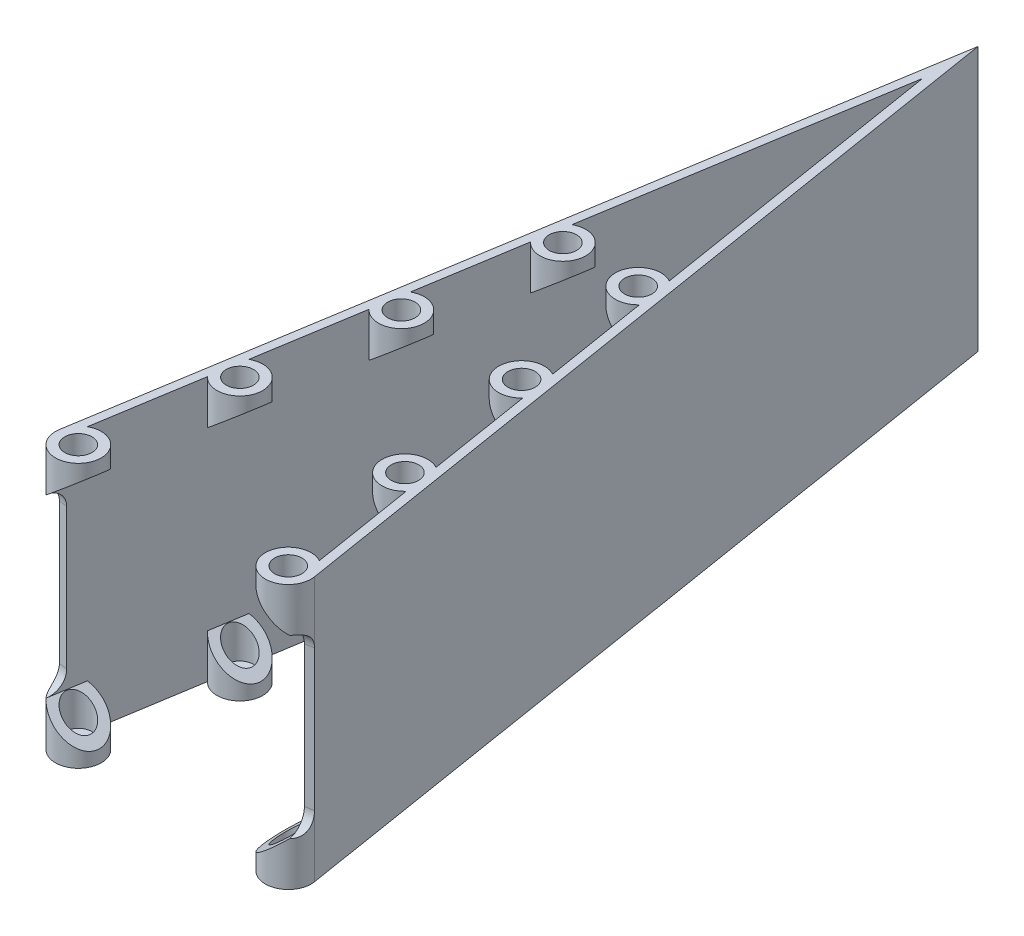
SolidWorks part; units mm, degrees
ref_plane "Front Plane" through (0, 0, 0) normal (0, 0, 1) x (1, 0, 0)
ref_plane "Top Plane" through (0, 0, 0) normal (0, 1, 0) x (1, 0, 0)
ref_plane "Right Plane" through (0, 0, 0) normal (1, 0, 0) x (0, 0, -1)
sketch "Sketch1" plane through (0, 0, 0) normal (0, 1, 0) x (1, 0, 0)
  line L0 (-13.5, 0) -> (13.5, 0) construction
  line L1 (-13.5, 0) -> (0, 83.7185)
  line L2 (0, 83.7185) -> (13.5, 0)
  line L3 (13.5, 0) -> (14.4872, 0.1592)
  line L4 (14.4872, 0.1592) -> (0, 90)
  line L5 (0, 90) -> (-14.4872, 0.1592)
  line L6 (-14.4872, 0.1592) -> (-13.5, 0)
  point P2 (0, 0)
  dimension "D1" = 90
  dimension "D2" = 90
  dimension "D4" = 1
  dimension "D5" = 27
  dimension "D3" = 90
extrude "Boss-Extrude1" add sketch "Sketch1" along normal blind 30
sketch "Sketch2" plane through (0, 0, 0) normal (0, 1, 0) x (1, 0, 0)
  line L0 (0, -1000) -> (0, 49000) construction
  line L1 (0, 83.7185) -> (13.5, 0) construction
  line L2 (0, 83.7185) -> (13.5, 0) construction
  line L3 (11.9204, -0.2547) -> (13.5, 0) construction
  line L4 (13.5, 0) -> (14.4872, 0.1592) construction
  line L5 (14.4872, 0.1592) -> (0, 90) construction
  line L6 (14.4872, 0.1592) -> (0, 90) construction
  circle A0 centre (11.9204, -0.2547) radius 2.6
  circle A1 centre (11.9204, -0.2547) radius 1.55
  circle A22 centre (9.3732, 15.5412) radius 1.55
  circle A23 centre (9.3732, 15.5412) radius 2.6
  circle A24 centre (6.8261, 31.3372) radius 1.55
  circle A25 centre (6.8261, 31.3372) radius 2.6
  circle A26 centre (4.2789, 47.1331) radius 1.55
  circle A27 centre (4.2789, 47.1331) radius 2.6
  circle A28 centre (-4.2789, 47.1331) radius 2.6
  circle A29 centre (-4.2789, 47.1331) radius 1.55
  circle A30 centre (-6.8261, 31.3372) radius 2.6
  circle A31 centre (-6.8261, 31.3372) radius 1.55
  circle A32 centre (-9.3732, 15.5412) radius 2.6
  circle A33 centre (-9.3732, 15.5412) radius 1.55
  circle A34 centre (-11.9204, -0.2547) radius 2.6
  circle A35 centre (-11.9204, -0.2547) radius 1.55
  dimension "D1" = 5.2
  dimension "D2" = 3.1
  dimension "D4" = 16
  dimension "D3" = 4
extrude "Boss-Extrude3" add sketch "Sketch2" along normal blind 5
sketch "Sketch4" plane through (0.3421, 0, 2.1218) normal (0.1592, 0, 0.9872) x (0.9872, 0, -0.1592)
  line L0 (9.1278, 5) -> (9.1278, 0) construction
  line L1 (14.3278, 5) -> (9.1278, 5) construction
  line L2 (13.3278, 30) -> (13.3278, 0) construction
  line L3 (9.1278, 5) -> (9.1278, 0) construction
  line L4 (14.3278, 5) -> (9.1278, 5) construction
  line L5 (13.3278, 30) -> (13.3278, 0) construction
  line L6 (13.3278, 5) -> (9.1278, 1.4758)
  line L7 (13.3278, 5) -> (9.1278, 5)
  line L8 (9.1278, 5) -> (9.1278, 1.4758)
  dimension "D1" = 40
extrude "Cut-Extrude1" cut sketch "Sketch4" against normal up to surface and the other way through all contours L7 L8 L6 region at (10.7357, 3.8253, 0.4458) up to face at (-8.5675, 5.5556, -30.5881)
sketch "Sketch5" plane through (-0.3421, 0, 2.1218) normal (-0.1592, 0, 0.9872) x (0.9872, 0, 0.1592)
  line L2 (-13.3278, 30) -> (-13.3278, 0) construction
  line L3 (-9.1278, 0) -> (-9.1278, 5) construction
  line L4 (-9.1278, 5) -> (-14.3278, 5) construction
  line L5 (-13.3278, 30) -> (-13.3278, 0) construction
  line L6 (-13.3278, 5) -> (-9.1278, 1.4758)
  line L7 (-13.3278, 5) -> (-9.1278, 5)
  line L8 (-9.1278, 5) -> (-9.1278, 1.4758)
  line L9 (-9.1278, 0) -> (-9.1278, 5)
  line L10 (-9.1278, 5) -> (-14.3278, 5)
  dimension "D1" = 40
extrude "Cut-Extrude2" cut sketch "Sketch5" against normal up to surface and the other way through all contours L8 L7 L6 region at (-10.7357, 3.8253, 0.4458) up to face at (8.5675, 5.5556, -30.5881)
ref_plane "Plane1" through (0, 15, 0) normal (0, 1, 0) x (1, 0, 0)
mirror "Mirror2" about plane through (0, 15, 0) normal (0, 1, 0) of "Cut-Extrude2", "Cut-Extrude1", "Boss-Extrude3"
fillet "Fillet1" radius 2 4 edges at (13.9936, 5, -0.0796) (13.9936, 25, -0.0796) (-13.9936, 5, -0.0796) (-13.9936, 25, -0.0796)
sketch "Sketch6" plane through (0, 0, 0) normal (0, -1, 0) x (1, 0, 0)
  arc A1 (14.4872, -0.1592) -> (13.1737, -2.0233) centre (11.9204, 0.2547) ccw construction
  arc A2 (11.2791, -13.7727) -> (10.6266, -17.8192) centre (9.3732, -15.5412) ccw construction
  arc A5 (8.7319, -29.5686) -> (8.0794, -33.6151) centre (6.8261, -31.3372) ccw construction
  arc A6 (6.1847, -45.3646) -> (5.5322, -49.4111) centre (4.2789, -47.1331) ccw construction
  arc A10 (-5.5322, -49.4111) -> (-6.1847, -45.3646) centre (-4.2789, -47.1331) ccw construction
  arc A11 (14.4872, -0.1592) -> (13.1737, -2.0233) centre (11.9204, 0.2547) ccw
  arc A12 (11.2791, -13.7727) -> (10.6266, -17.8192) centre (9.3732, -15.5412) ccw
  arc A13 (-8.0794, -33.6151) -> (-8.7319, -29.5686) centre (-6.8261, -31.3372) ccw construction
  arc A14 (-10.6266, -17.8192) -> (-11.2791, -13.7727) centre (-9.3732, -15.5412) ccw construction
  arc A15 (8.7319, -29.5686) -> (8.0794, -33.6151) centre (6.8261, -31.3372) ccw
  arc A16 (6.1847, -45.3646) -> (5.5322, -49.4111) centre (4.2789, -47.1331) ccw
  arc A17 (-13.1737, -2.0233) -> (-14.4872, -0.1592) centre (-11.9204, 0.2547) ccw construction
  arc A18 (-5.5322, -49.4111) -> (-6.1847, -45.3646) centre (-4.2789, -47.1331) ccw
  arc A19 (-8.0794, -33.6151) -> (-8.7319, -29.5686) centre (-6.8261, -31.3372) ccw
  circle A22 centre (4.2789, -47.1331) radius 2.6
  circle A24 centre (6.8261, -31.3372) radius 2.6
  circle A27 centre (9.3732, -15.5412) radius 2.6
  circle A28 centre (11.9204, 0.2547) radius 2.6
  arc A30 (-10.6266, -17.8192) -> (-11.2791, -13.7727) centre (-9.3732, -15.5412) ccw
  arc A31 (-13.1737, -2.0233) -> (-14.4872, -0.1592) centre (-11.9204, 0.2547) ccw
  circle A32 centre (-11.9204, 0.2547) radius 2.6
  circle A33 centre (-9.3732, -15.5412) radius 2.6
  circle A34 centre (-6.8261, -31.3372) radius 2.6
  circle A35 centre (-4.2789, -47.1331) radius 2.6
  circle M23 centre (11.9204, 0.2547) radius 1.55
  circle M24 centre (9.3732, -15.5412) radius 1.55
  circle M25 centre (6.8261, -31.3372) radius 1.55
  circle M26 centre (4.2789, -47.1331) radius 1.55
  circle M71 centre (-4.2789, -47.1331) radius 1.55
  circle M72 centre (-6.8261, -31.3372) radius 1.55
  circle M73 centre (-9.3732, -15.5412) radius 1.55
  circle M74 centre (-11.9204, 0.2547) radius 1.55
extrude "Boss-Extrude4" add sketch "Sketch6" against normal blind 1 contours M26 | M25 | M24 | M23 | M74 | M73 | M72 | M71 region at (11.9204, 0, 0.2547) region at (9.3732, 0, -15.5412) region at (6.8261, 0, -31.3372) region at (4.2789, 0, -47.1331) region at (-4.2789, 0, -47.1331) region at (-6.8261, 0, -31.3372) region at (-9.3732, 0, -15.5412) region at (-11.9204, 0, 0.2547)
equation "\"D2@Sketch1\"=\"D1@Sketch1\""
